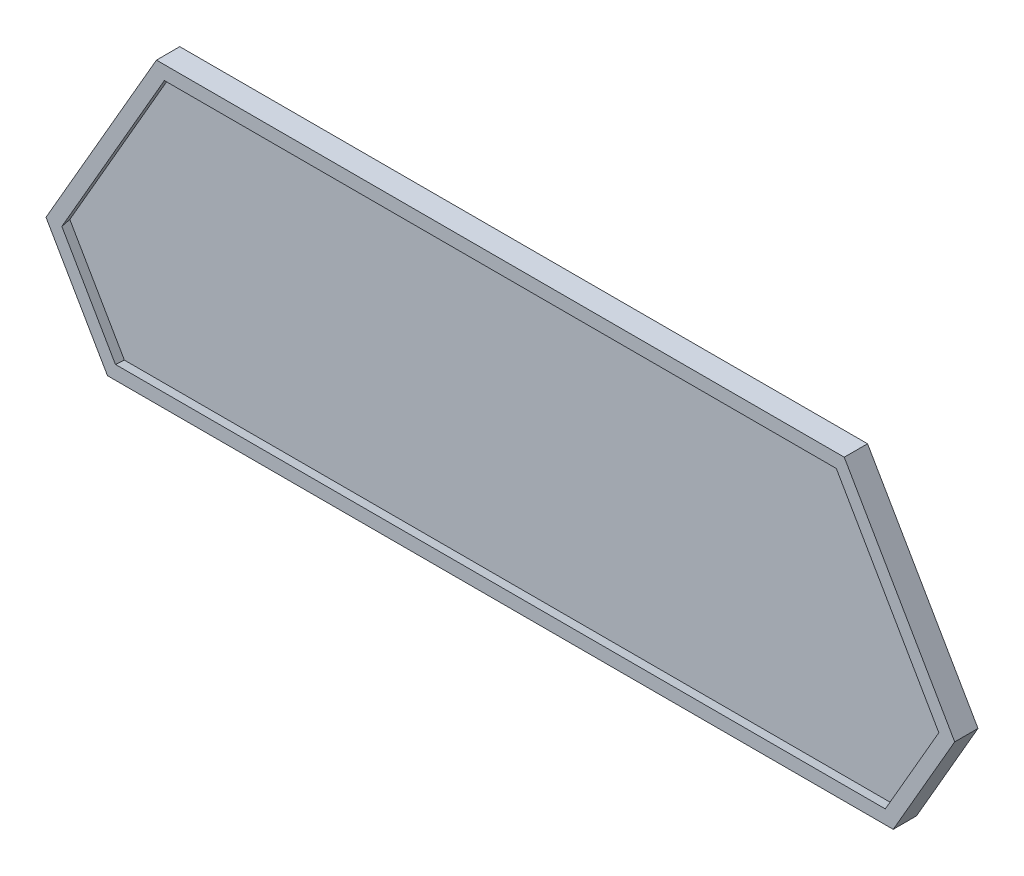
SolidWorks part; units mm, degrees
ref_plane "Plan de face" through (0, 0, 0) normal (0, 0, 1) x (1, 0, 0)
ref_plane "Plan de dessus" through (0, 0, 0) normal (0, 1, 0) x (1, 0, 0)
ref_plane "Plan de droite" through (0, 0, 0) normal (1, 0, 0) x (0, 0, -1)
sketch "Esquisse1" plane through (0, 0, 0) normal (0, 0, 1) x (1, 0, 0)
  line L30 (32.25, -42.5625) -> (2.7, -42.5625)
  line L31 (32.25, -44.0446) -> (32.25, -42.5625)
  line L32 (42.75, -44.0446) -> (32.25, -44.0446)
  line L33 (42.75, -42.5625) -> (42.75, -44.0446)
  line L34 (57.7649, -42.5625) -> (42.75, -42.5625)
  line L35 (65.7427, -28.7446) -> (57.7649, -42.5625)
  line L36 (50.4068, -2.1821) -> (65.7427, -28.7446)
  line L37 (-50.4068, -2.1821) -> (50.4068, -2.1821)
  line L38 (-65.7427, -28.7446) -> (-50.4068, -2.1821)
  line L39 (-57.7649, -42.5625) -> (-65.7427, -28.7446)
  line L40 (-42.75, -42.5625) -> (-57.7649, -42.5625)
  line L41 (-42.75, -44.0446) -> (-42.75, -42.5625)
  line L42 (-32.25, -44.0446) -> (-42.75, -44.0446)
  line L43 (-32.25, -42.5625) -> (-32.25, -44.0446)
  line L44 (-2.7, -42.5625) -> (-32.25, -42.5625)
  line L45 (-2.7, -44.7446) -> (-2.7, -42.5625)
  line L46 (-59.0248, -44.7446) -> (-2.7, -44.7446)
  line L47 (-68.2624, -28.7446) -> (-59.0248, -44.7446)
  line L48 (-51.6667, 0) -> (-68.2624, -28.7446)
  line L49 (51.6667, 0) -> (-51.6667, 0)
  line L50 (68.2624, -28.7446) -> (51.6667, 0)
  line L51 (59.0248, -44.7446) -> (68.2624, -28.7446)
  line L52 (2.7, -44.7446) -> (59.0248, -44.7446)
  line L53 (2.7, -42.5625) -> (2.7, -44.7446)
  line L70 (-59.0248, -44.7446) -> (2.7, -44.7446)
  line L71 (-68.2624, -28.7446) -> (-59.0248, -44.7446)
  line L72 (-51.6667, 0) -> (-68.2624, -28.7446)
  line L73 (51.6667, 0) -> (-51.6667, 0)
  line L74 (68.2624, -28.7446) -> (51.6667, 0)
  line L75 (59.0248, -44.7446) -> (68.2624, -28.7446)
  line L76 (2.7, -44.7446) -> (59.0248, -44.7446)
  dimension "D1" = 0
extrude "Boss.-Extru.1" add sketch "Esquisse1" along normal blind 2
sketch "Esquisse2" plane through (0, 0, 2) normal (0, 0, 1) x (1, 0, 0)
  line L6 (-68.2624, -28.7446) -> (-59.0248, -44.7446)
  line L7 (-59.0248, -44.7446) -> (59.0248, -44.7446)
  line L8 (59.0248, -44.7446) -> (68.2624, -28.7446)
  line L9 (68.2624, -28.7446) -> (51.6667, 0)
  line L10 (51.6667, 0) -> (-51.6667, 0)
  line L11 (-51.6667, 0) -> (-68.2624, -28.7446)
  line L12 (-68.2624, -28.7446) -> (-59.0248, -44.7446)
  line L13 (-59.0248, -44.7446) -> (59.0248, -44.7446)
  line L14 (59.0248, -44.7446) -> (68.2624, -28.7446)
  line L15 (68.2624, -28.7446) -> (51.6667, 0)
  line L16 (51.6667, 0) -> (-51.6667, 0)
  line L17 (-51.6667, 0) -> (-68.2624, -28.7446)
  dimension "D1" = 0
extrude "Extru.-Mince1" add sketch "Esquisse2" along normal blind 1.5 draft 10 thin draft outward yes thin type one direction reverse wall 1.8
sketch "Esquisse3" plane through (0, 0, 0) normal (0, 0, -1) x (-1, 0, 0)
  line L6 (59.0248, -44.7446) -> (68.2624, -28.7446)
  line L7 (68.2624, -28.7446) -> (51.6667, 0)
  line L8 (51.6667, 0) -> (-51.6667, 0)
  line L9 (-51.6667, 0) -> (-68.2624, -28.7446)
  line L10 (-68.2624, -28.7446) -> (-59.0248, -44.7446)
  line L11 (-59.0248, -44.7446) -> (59.0248, -44.7446)
  line L12 (59.0248, -44.7446) -> (68.2624, -28.7446)
  line L13 (68.2624, -28.7446) -> (51.6667, 0)
  line L14 (51.6667, 0) -> (-51.6667, 0)
  line L15 (-51.6667, 0) -> (-68.2624, -28.7446)
  line L16 (-68.2624, -28.7446) -> (-59.0248, -44.7446)
  line L17 (-59.0248, -44.7446) -> (59.0248, -44.7446)
  dimension "D1" = 0
extrude "Enlèv. de mat.-Extru.-Mince1" cut sketch "Esquisse3" against normal through all thin thin type one direction wall 1.9
